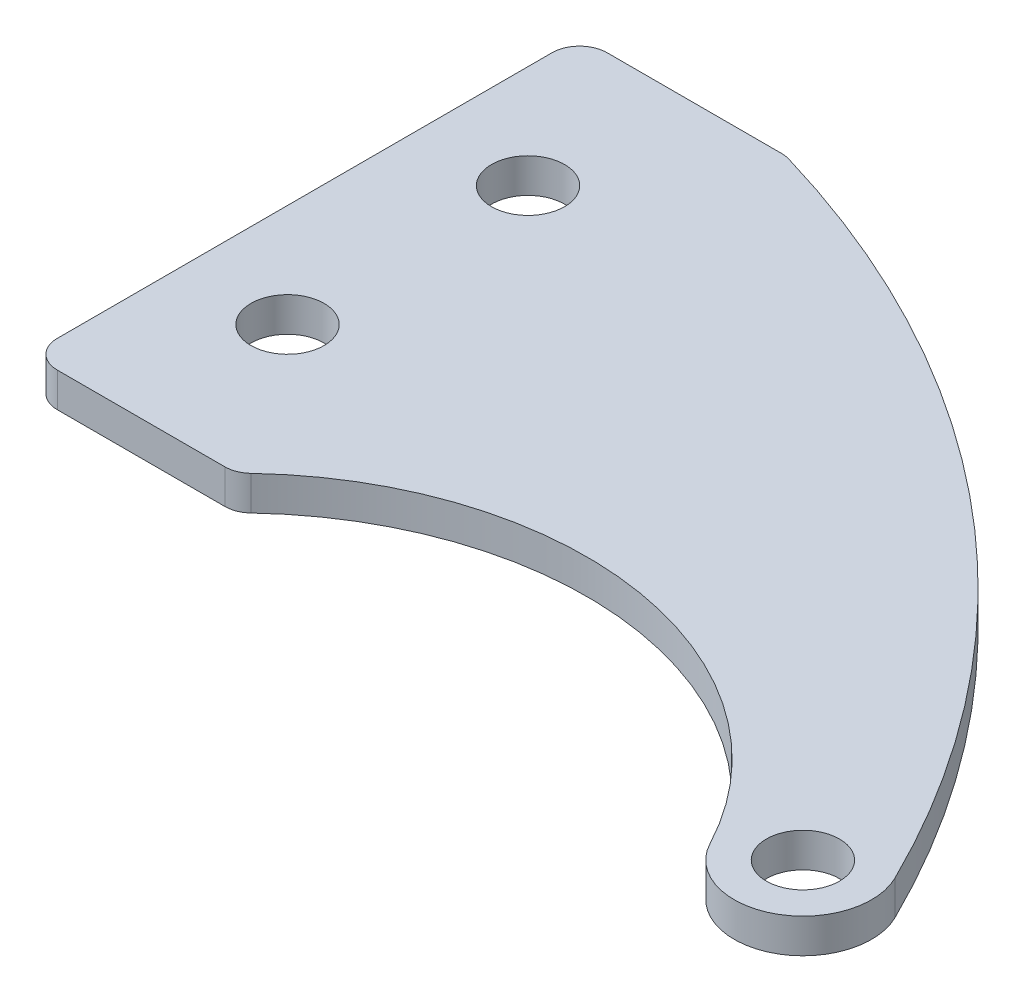
SolidWorks part; units mm, degrees
material "6061-T6 (SS)"
ref_plane "Front" through (0, 0, 0) normal (0, 0, 1) x (1, 0, 0)
ref_plane "Top" through (0, 0, 0) normal (0, 1, 0) x (1, 0, 0)
ref_plane "Right" through (0, 0, 0) normal (1, 0, 0) x (0, 0, -1)
sketch "Sketch1" plane through (0, 0, 0) normal (0, 1, 0) x (1, 0, 0)
  line L1 (0, 50.8) -> (19.05, 50.8)
  line L4 (0, 50.8) -> (0, 0)
  line L6 (0, 0) -> (19.05, 0)
  arc A0 (81.8992, -1.9621) -> (70.584, -7.7262) centre (76.2, -4.7625) cw
  arc A3 (19.05, 0) -> (70.584, -7.7262) centre (41.9743, -22.8241) cw
  arc A6 (81.8992, -1.9621) -> (19.05, 50.8) centre (-9.2873, -46.7682) ccw
  point P7 (42.6399, -18.2238)
  dimension "D1" = 19.05
  dimension "D2" = 4.7625
  dimension "D3" = 6.35
  dimension "D4" = 76.2
  dimension "D6" = 9.525
  dimension "D7" = 101.6
  dimension "D5" = 50.8
extrude "Boss-Extrude1" add sketch "Sketch1" along normal blind 3.175
hole_wizard "1/4 Clearance Hole2" positions "Sketch4" profile "Sketch3" hole size "1/4" standard "ANSI Inch" end condition through all
sketch "Sketch4" plane through (0, 0, 0) normal (0, -1, 0) x (-1, 0, 0)
  point P0 (-76.2, -4.7625)
sketch "Sketch3" plane through (76.2, 0, 4.7625) normal (1, 0, 0) x (0, 0, -1)
  line L0 (0, 0) -> (0, 3.175)
  line L1 (0, 3.175) -> (3.3782, 3.175)
  line L2 (3.3782, 3.175) -> (3.3782, 0)
  line L5 (3.3782, 0) -> (0, 0)
  line L11 (0, -6.35) -> (0, 107.95) construction
  dimension "Thru Hole Dia." = 6.7564
  dimension "Thru Hole Depth" = 3.175
hole_wizard "1/4 Clearance Hole1" positions "Sketch7" profile "Sketch8" hole size "1/4" standard "ANSI Inch" end condition through all
sketch "Sketch7" plane through (0, 3.175, 0) normal (0, 1, 0) x (1, 0, 0)
  line L9 (9.525, 0) -> (9.525, 14.2875) construction
  line L10 (0, 0) -> (19.05, 0) construction
  line L11 (9.525, 14.2875) -> (9.525, 36.5125) construction
  line L12 (9.525, 36.5125) -> (9.525, 50.8) construction
  line L13 (19.05, 50.8) -> (0, 50.8) construction
  point P0 (9.525, 36.5125)
  point P2 (9.525, 14.2875)
  dimension "D1" = 22.225
sketch "Sketch8" plane through (9.525, 3.175, -36.5125) normal (1, 0, 0) x (0, 0, 1)
  line L0 (0, 0) -> (0, 3.175)
  line L1 (0, 3.175) -> (3.3782, 3.175)
  line L2 (3.3782, 3.175) -> (3.3782, 0)
  line L5 (3.3782, 0) -> (0, 0)
  line L11 (0, -6.35) -> (0, 107.95) construction
  dimension "Thru Hole Dia." = 6.7564
  dimension "Thru Hole Depth" = 3.175
fillet "Fillet1" radius 2.54 4 edges at (19.05, 1.5875, 0) (0, 1.5875, 0) (0, 1.5875, -50.8) (19.05, 1.5875, -50.8)
